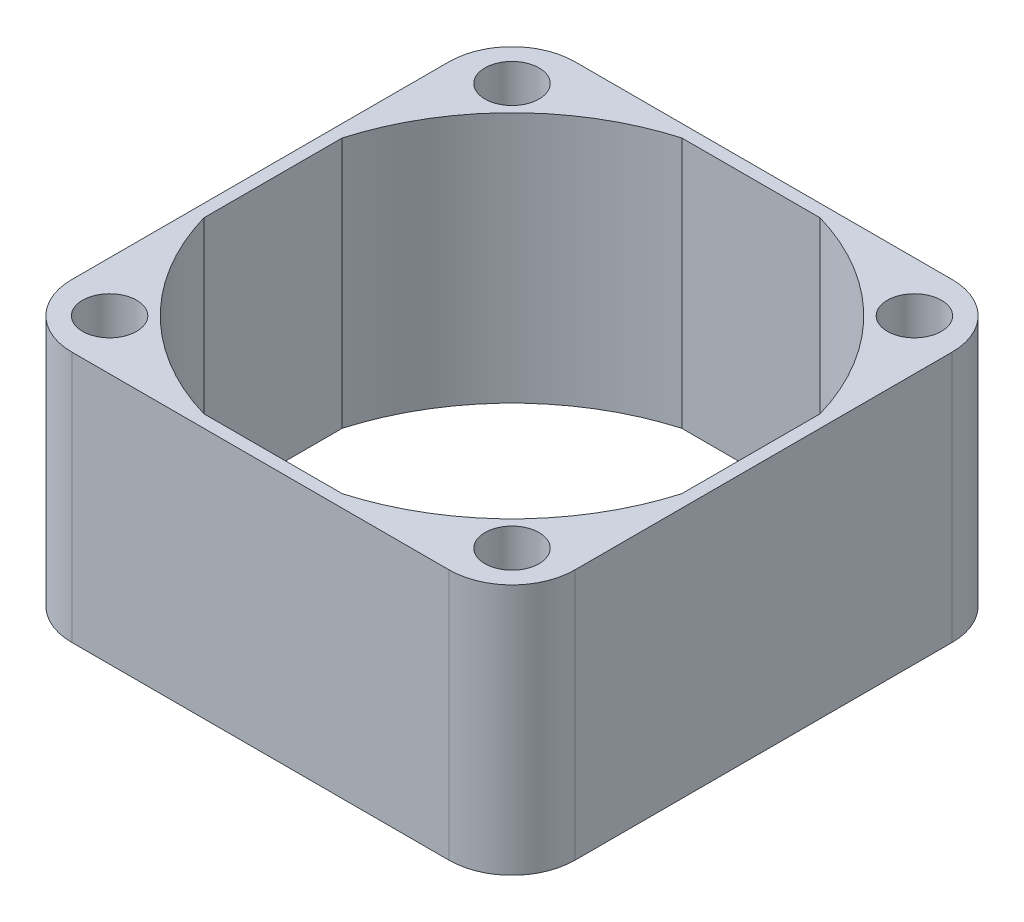
SolidWorks part; units mm, degrees
material "6061-T6 (SS)"
ref_plane "Front Plane" through (0, 0, 0) normal (0, 0, 1) x (1, 0, 0)
ref_plane "Top Plane" through (0, 0, 0) normal (0, 1, 0) x (1, 0, 0)
ref_plane "Right Plane" through (0, 0, 0) normal (1, 0, 0) x (0, 0, -1)
ref_axis "Axis1" through (0, 0, 55) along (0, 0, -1)
sketch "Sketch1" plane through (0, 0, 0) normal (0, 1, 0) x (1, 0, 0)
  line L0 (-5.5, 19) -> (5.5, 19)
  line L1 (-20, 20) -> (20, 20)
  line L2 (-20, 20) -> (-20, -20)
  line L3 (-20, -20) -> (20, -20)
  line L4 (20, 20) -> (20, -20)
  line L5 (-20, 20) -> (20, -20) construction
  line L6 (-20, -20) -> (20, 20) construction
  line L7 (-16, 16) -> (16, 16) construction
  line L8 (-16, 16) -> (-16, -16) construction
  line L9 (-16, -16) -> (16, -16) construction
  line L10 (16, 16) -> (16, -16) construction
  line L11 (-16, 16) -> (16, -16) construction
  line L12 (-16, -16) -> (16, 16) construction
  line L13 (19, 5.5) -> (19, -5.5)
  line L14 (-5.5, -19) -> (5.5, -19)
  line L15 (-19, 5.5) -> (-19, -5.5)
  line L16 (19, -5.5) -> (19, -19) construction
  line L17 (19, 19) -> (19, -19) construction
  line L18 (5.5, -19) -> (19, -19) construction
  line L19 (-19, -19) -> (19, -19) construction
  line L20 (-19, -19) -> (-5.5, -19) construction
  line L21 (-19, -5.5) -> (-19, -19) construction
  line L22 (-19, 19) -> (-19, -19) construction
  line L23 (-19, 19) -> (-19, 5.5) construction
  line L24 (-19, 19) -> (-5.5, 19) construction
  line L25 (-19, 19) -> (19, 19) construction
  line L26 (5.5, 19) -> (19, 19) construction
  line L27 (19, 19) -> (19, 5.5) construction
  circle A0 centre (16, 16) radius 2.15
  circle A1 centre (16, -16) radius 2.15
  circle A2 centre (-16, -16) radius 2.15
  circle A3 centre (-16, 16) radius 2.15
  arc A4 (19, 5.5) -> (5.5, 19) centre (0, 0) ccw
  arc A5 (19, -5.5) -> (19, 5.5) centre (0, 0) ccw construction
  arc A6 (-5.5, -19) -> (5.5, -19) centre (0, 0) ccw construction
  arc A7 (5.5, -19) -> (19, -5.5) centre (0, 0) ccw
  arc A8 (-19, 5.5) -> (-19, -5.5) centre (0, 0) ccw construction
  arc A9 (-19, -5.5) -> (-5.5, -19) centre (0, 0) ccw
  arc A10 (5.5, 19) -> (-5.5, 19) centre (0, 0) ccw construction
  arc A11 (-5.5, 19) -> (-19, 5.5) centre (0, 0) ccw
  point P0 (0, 0)
  point P6 (0, 0)
  dimension "D3" = 4.3
  dimension "D1" = 40
  dimension "D2" = 32
  dimension "D4" = 1
  dimension "D5" = 11
extrude "Boss-Extrude1" add sketch "Sketch1" along normal blind 20
fillet "Fillet1" radius 5 4 edges at (-20, 10, 20) (20, 10, 20) (20, 10, -20) (-20, 10, -20)
